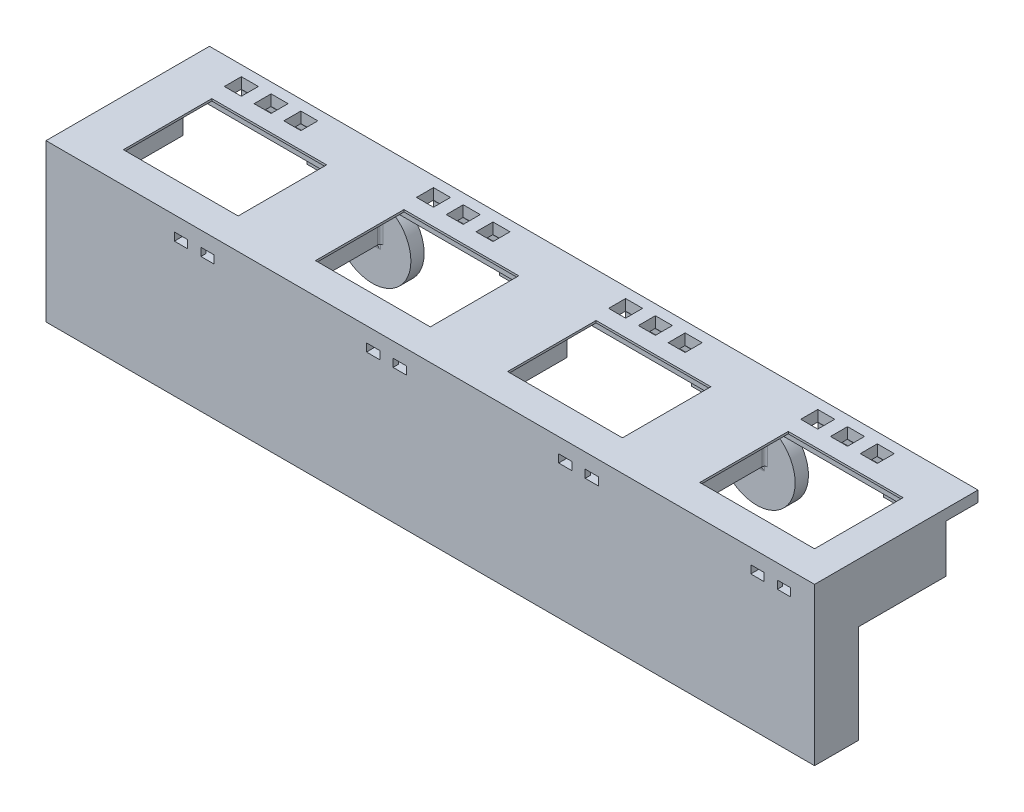
SolidWorks part; units mm, degrees
ref_plane "Front Plane" through (0, 0, 0) normal (0, 0, 1) x (1, 0, 0)
ref_plane "Top Plane" through (0, 0, 0) normal (0, 1, 0) x (1, 0, 0)
ref_plane "Right Plane" through (0, 0, 0) normal (1, 0, 0) x (0, 0, -1)
sketch "Sketch1" plane through (0, 0, 0) normal (0, 1, 0) x (1, 0, 0)
  line L0 (23.7457, 59.297) -> (23.7457, 2.797)
  line L1 (33.7457, 49.297) -> (86.0457, 49.297)
  line L2 (33.7457, 49.297) -> (33.7457, 12.797)
  line L3 (33.7457, 12.797) -> (86.0457, 12.797)
  line L4 (86.0457, 49.297) -> (86.0457, 12.797)
  line L5 (23.7457, 2.797) -> (96.0457, 2.797)
  line L6 (96.0457, 59.297) -> (96.0457, 2.797)
  line L7 (23.7457, 59.297) -> (96.0457, 59.297)
  dimension "D1" = 36.5
  dimension "D2" = 52.3
  dimension "D3" = 10
extrude "Boss-Extrude1" add sketch "Sketch1" along normal blind 3.3
sketch "Sketch2" plane through (0, 0, 0) normal (0, -1, 0) x (1, 0, 0)
  line L0 (96.0457, -2.797) -> (96.0457, -59.297) construction
  line L1 (23.7457, -2.797) -> (96.0457, -2.797)
  line L2 (23.7457, -2.797) -> (23.7457, -4.797)
  line L3 (23.7457, -4.797) -> (96.0457, -4.797)
  line L4 (96.0457, -2.797) -> (96.0457, -4.797)
  dimension "D1" = 2
extrude "Boss-Extrude2" add sketch "Sketch2" along normal blind 45
sketch "Sketch3" plane through (0, 0, -4.797) normal (0, 0, -1) x (-1, 0, 0)
  line L0 (-23.7457, -45) -> (-96.0457, -45) construction
  line L1 (-96.0457, 0) -> (-94.0457, 0)
  line L2 (-96.0457, 0) -> (-96.0457, -45)
  line L3 (-96.0457, -45) -> (-94.0457, -45)
  line L4 (-94.0457, 0) -> (-94.0457, -45)
  line L6 (-23.7457, 0) -> (-25.7457, 0)
  line L7 (-23.7457, 0) -> (-23.7457, -45)
  line L8 (-23.7457, -45) -> (-25.7457, -45)
  line L9 (-25.7457, 0) -> (-25.7457, -45)
  dimension "D1" = 2
  dimension "D2" = 2
extrude "Boss-Extrude3" add sketch "Sketch3" along normal up to surface (54.5 mm away) up to face at (59.8957, 1.65, -59.297)
sketch "Sketch5" plane through (0, 3.3, 0) normal (0, 1, 0) x (1, 0, 0)
  line L1 (23.7457, 59.297) -> (96.0457, 59.297)
  line L2 (23.7457, 59.297) -> (23.7457, 2.797)
  line L3 (23.7457, 2.797) -> (96.0457, 2.797)
  line L4 (96.0457, 59.297) -> (96.0457, 2.797)
  line L9 (41.2457, 47.697) -> (41.2457, 14.397)
  line L10 (41.2457, 47.697) -> (84.4457, 47.697)
  line L11 (84.4457, 47.697) -> (84.4457, 14.397)
  line L12 (84.4457, 14.397) -> (41.2457, 14.397)
  point P6 (34.2457, 48.797)
  point P7 (34.2457, 13.297)
  point P8 (85.5457, 13.297)
  point P9 (85.5457, 48.797)
  dimension "D2" = 11.6
  dimension "D1" = 17.5
  dimension "D3" = 11.6
  dimension "D4" = 11.6
extrude "Boss-Extrude6" add sketch "Sketch5" along normal blind 0.8
sketch "Sketch6" plane through (0, 0, -4.797) normal (0, 0, -1) x (-1, 0, 0)
  line L0 (-25.7457, 0) -> (-25.7457, -45) construction
  line L1 (-94.0457, 0) -> (-25.7457, 0)
  line L2 (-94.0457, 0) -> (-94.0457, -1.5)
  line L3 (-94.0457, -1.5) -> (-25.7457, -1.5)
  line L4 (-25.7457, 0) -> (-25.7457, -1.5)
  dimension "D1" = 1.5
extrude "Boss-Extrude7" add sketch "Sketch6" along normal blind 7.8
sketch "Sketch7" plane through (0, 0, -4.797) normal (0, 0, -1) x (-1, 0, 0)
  line L0 (-94.0457, -1.5) -> (-87.0457, -1.5) construction
  line L1 (-94.0457, -1.5) -> (-25.7457, -1.5) construction
  line L2 (-87.0457, -1.5) -> (-72.0457, -1.5) construction
  line L3 (-87.0457, -1.5) -> (-87.0457, -4.5)
  line L4 (-87.0457, -4.5) -> (-72.0457, -4.5)
  line L5 (-72.0457, -4.5) -> (-72.0457, -1.5)
  line L6 (-72.0457, -1.5) -> (-70.5457, -1.5)
  line L7 (-70.5457, -1.5) -> (-70.5457, -6)
  line L8 (-70.5457, -6) -> (-88.5457, -6)
  line L9 (-88.5457, -6) -> (-88.5457, -1.5)
  line L10 (-88.5457, -1.5) -> (-87.0457, -1.5)
  dimension "D1" = 7
  dimension "D2" = 15
  dimension "D3" = 3
  dimension "D4" = 1.5
  dimension "D5" = 1.5
  dimension "D6" = 1.5
extrude "Boss-Extrude8" add sketch "Sketch7" along normal up to surface (7.8 mm away) up to face at (59.8957, -0.75, -12.597)
sketch "Sketch8" plane through (0, 0, -59.297) normal (0, 0, -1) x (-1, 0, 0)
  line L0 (-94.0457, 0) -> (-25.7457, 0) construction
  line L1 (-88.5457, -6) -> (-70.503, -6)
  line L2 (-88.5457, -6) -> (-88.5457, 0)
  line L3 (-88.5457, 0) -> (-70.503, 0)
  line L4 (-70.503, -6) -> (-70.503, 0)
  line L6 (-87.0457, -1.5) -> (-72.0457, -1.5)
  line L7 (-87.0457, -1.5) -> (-87.0457, -4.5)
  line L8 (-87.0457, -4.5) -> (-72.0457, -4.5)
  line L9 (-72.0457, -1.5) -> (-72.0457, -4.5)
extrude "Boss-Extrude9" add sketch "Sketch8" against normal up to surface (10 mm away) up to face at (59.8957, 1.65, -49.297)
sketch "Sketch9" plane through (0, 0, 0) normal (0, -1, 0) x (1, 0, 0)
  line L0 (86.0457, -49.297) -> (86.0457, -44.297) construction
  line L1 (86.0457, -12.797) -> (86.0457, -49.297) construction
  line L2 (86.0457, -44.297) -> (90.0457, -44.297)
  line L3 (90.0457, -44.297) -> (90.0457, -17.797)
  line L4 (90.0457, -17.797) -> (86.0457, -17.797)
  line L5 (86.0457, -17.797) -> (86.0457, -12.797) construction
  line L6 (86.0457, -44.297) -> (86.0457, -17.797)
  dimension "D1" = 5
  dimension "D2" = 5
  dimension "D3" = 4
extrude "Cut-Extrude1" cut sketch "Sketch9" against normal blind 2
sketch "Sketch10" plane through (0, 0, -59.297) normal (0, 0, -1) x (-1, 0, 0)
  line L0 (-94.0457, 0) -> (-94.0457, -45) construction
  line L1 (-96.0457, -45) -> (-94.0457, -45)
  line L2 (-96.0457, -45) -> (-96.0457, -15)
  line L3 (-96.0457, -15) -> (-94.0457, -15)
  line L4 (-94.0457, -45) -> (-94.0457, -15)
  dimension "D1" = 30
extrude "Cut-Extrude2" cut sketch "Sketch10" against normal blind 40
sketch "Sketch11" plane through (0, -1.5, 0) normal (0, -1, 0) x (1, 0, 0)
  line L0 (94.0457, -4.797) -> (94.0457, -7.197) construction
  line L1 (94.0457, -4.797) -> (88.5457, -4.797) construction
  line L2 (94.0457, -12.597) -> (94.0457, -4.797) construction
  line L3 (94.0457, -7.197) -> (94.0457, -8.197)
  line L4 (94.0457, -8.197) -> (92.0457, -8.197)
  line L5 (92.0457, -8.197) -> (92.0457, -7.197)
  line L6 (92.0457, -7.197) -> (94.0457, -7.197)
  line L7 (25.7457, -7.197) -> (27.7457, -7.197)
  line L8 (25.7457, -12.597) -> (25.7457, -4.797) construction
  line L9 (27.7457, -7.197) -> (27.7457, -8.197)
  line L10 (27.7457, -8.197) -> (25.7457, -8.197)
  line L11 (25.7457, -8.197) -> (25.7457, -7.197)
  line L12 (70.5457, -4.797) -> (25.7457, -4.797) construction
  dimension "D1" = 2.4
  dimension "D2" = 2
  dimension "D3" = 1
  dimension "D4" = 2.4
  dimension "D5" = 1
  dimension "D6" = 2
extrude "Boss-Extrude10" add sketch "Sketch11" along normal blind 20
sketch "Sketch13" plane through (0, 0, -59.297) normal (0, 0, -1) x (-1, 0, 0)
  line L13 (-87.0457, -1.5) -> (-72.0457, -1.5)
  line L14 (-87.0457, -1.5) -> (-87.0457, -4.5)
  line L15 (-87.0457, -4.5) -> (-72.0457, -4.5)
  line L16 (-72.0457, -1.5) -> (-72.0457, -4.5)
  line L24 (-96.0457, 4.1) -> (-96.0457, -15)
  line L25 (-96.0457, -15) -> (-94.0457, -15)
  line L26 (-94.0457, -15) -> (-94.0457, 0)
  line L27 (-94.0457, 0) -> (-88.5457, 0)
  line L28 (-88.5457, 0) -> (-88.5457, -6)
  line L29 (-88.5457, -6) -> (-70.503, -6)
  line L30 (-70.503, -6) -> (-70.503, 0)
  line L31 (-70.503, 0) -> (-25.7457, 0)
  line L32 (-25.7457, 0) -> (-25.7457, -45)
  line L33 (-25.7457, -45) -> (-23.7457, -45)
  line L34 (-23.7457, -45) -> (-23.7457, 4.1)
  line L35 (-23.7457, 4.1) -> (-96.0457, 4.1)
  line L36 (-96.0457, 4.1) -> (-96.0457, -15)
  line L37 (-96.0457, -15) -> (-94.0457, -15)
  line L38 (-94.0457, -15) -> (-94.0457, 0)
  line L39 (-94.0457, 0) -> (-88.5457, 0)
  line L40 (-88.5457, 0) -> (-88.5457, -6)
  line L41 (-88.5457, -6) -> (-70.503, -6)
  line L42 (-70.503, -6) -> (-70.503, 0)
  line L43 (-70.503, 0) -> (-25.7457, 0)
  line L44 (-25.7457, 0) -> (-25.7457, -45)
  line L45 (-25.7457, -45) -> (-23.7457, -45)
  line L46 (-23.7457, -45) -> (-23.7457, 4.1)
  line L47 (-23.7457, 4.1) -> (-96.0457, 4.1)
  dimension "D1" = 0
extrude "Boss-Extrude11" add sketch "Sketch13" along normal blind 5
sketch "Sketch12" plane through (0, 4.1, 0) normal (0, 1, 0) x (1, 0, 0)
  line L0 (23.7457, 60.297) -> (39.7457, 60.297) construction
  line L1 (23.7457, 64.297) -> (23.7457, 2.797) construction
  line L2 (39.7457, 60.297) -> (39.7457, 64.297) construction
  line L4 (45.9457, 60.297) -> (50.9457, 60.297) construction
  line L5 (39.7457, 60.297) -> (45.9457, 60.297)
  line L6 (39.7457, 60.297) -> (39.7457, 54.097)
  line L7 (39.7457, 54.097) -> (45.9457, 54.097)
  line L8 (45.9457, 60.297) -> (45.9457, 54.097)
  line L10 (50.9457, 60.297) -> (57.1457, 60.297)
  line L11 (50.9457, 60.297) -> (50.9457, 54.097)
  line L12 (50.9457, 54.097) -> (57.1457, 54.097)
  line L13 (57.1457, 60.297) -> (57.1457, 54.097)
  line L14 (23.7457, 64.297) -> (96.0457, 64.297) construction
  dimension "D1" = 4
  dimension "D2" = 16
  dimension "D3" = 6.2
  dimension "D4" = 6.2
  dimension "D5" = 5
  dimension "D6" = 6.2
  dimension "D7" = 6.2
extrude "Cut-Extrude3" cut sketch "Sketch12" against normal blind 10
sketch "Sketch14" plane through (0, 0, 0) normal (0, -1, 0) x (1, 0, 0)
  line L0 (88.5457, -49.297) -> (88.5457, -64.297) construction
  line L1 (70.503, -49.297) -> (88.5457, -49.297)
  line L2 (70.503, -49.297) -> (70.503, -54.297)
  line L3 (70.503, -54.297) -> (88.5457, -54.297)
  line L4 (88.5457, -49.297) -> (88.5457, -54.297)
  dimension "D1" = 5
extrude "Cut-Extrude4" cut sketch "Sketch14" along normal blind 25
sketch "Sketch15" plane through (0, 0, -64.297) normal (0, 0, -1) x (-1, 0, 0)
  line L1 (-100.1161, -15.1013) -> (-70.503, -15.1013)
  line L2 (-100.1161, -15.1013) -> (-100.1161, 0)
  line L3 (-100.1161, 0) -> (-70.503, 0)
  line L4 (-70.503, -15.1013) -> (-70.503, 0)
extrude "Cut-Extrude5" cut sketch "Sketch15" against normal blind 2
sketch "Sketch17" plane through (0, 0, 0) normal (0, -1, 0) x (1, 0, 0)
  line L1 (88.5457, -54.297) -> (94.0457, -54.297)
  line L2 (88.5457, -54.297) -> (88.5457, -62.297)
  line L3 (88.5457, -62.297) -> (94.0457, -62.297)
  line L4 (94.0457, -54.297) -> (94.0457, -62.297)
extrude "Boss-Extrude12" add sketch "Sketch17" along normal up to surface (6 mm away) up to face at (79.5244, -6, -58.297)
sketch "Sketch20" plane through (0, 0, -19.297) normal (0, 0, -1) x (-1, 0, 0)
  line L0 (-94.0457, -21.5) -> (-94.0457, -1.5) construction
  line L1 (-96.0457, -15) -> (-94.0457, -15)
  line L2 (-96.0457, -15) -> (-96.0457, -18)
  line L3 (-96.0457, -18) -> (-94.0457, -18)
  line L4 (-94.0457, -15) -> (-94.0457, -18)
  dimension "D1" = 3
extrude "Boss-Extrude14" add sketch "Sketch20" along normal up to surface (43 mm away) up to face at (86.8648, -7, -62.297)
sketch "Sketch21" plane through (0, 0, -62.297) normal (0, 0, -1) x (-1, 0, 0)
  line L0 (-96.0457, -18) -> (-94.0457, -18) construction
  circle A0 centre (-95.0457, -18) radius 14.5
  dimension "D1" = 29
extrude "Boss-Extrude15" add sketch "Sketch21" against normal blind 8
sketch "Sketch22" plane through (0, 0, -62.297) normal (0, 0, -1) x (-1, 0, 0)
  circle A0 centre (-95.0457, -18) radius 12.75
  dimension "D1" = 25.5
extrude "Cut-Extrude6" cut sketch "Sketch22" against normal blind 6
fillet "Fillet1" radius 2 3 edges at (96.0457, -10.7673, -54.297) (95.0457, -18, -54.297) (94.0457, -9, -54.297)
sketch "Sketch23" plane through (0, 0, 0) normal (0, -1, 0) x (1, 0, 0)
  line L1 (39.7457, -54.097) -> (57.154, -54.097)
  line L2 (39.7457, -54.097) -> (39.7457, -53.097)
  line L3 (39.7457, -53.097) -> (57.154, -53.097)
  line L4 (57.154, -54.097) -> (57.154, -53.097)
  dimension "D1" = 1
extrude "Boss-Extrude16" add sketch "Sketch23" along normal blind 2
sketch "Sketch24" plane through (0, 0, -54.097) normal (0, 0, -1) x (-1, 0, 0)
  line L0 (-57.154, -2) -> (-54.754, -2) construction
  line L1 (-39.7457, -2) -> (-57.154, -2) construction
  line L2 (-54.754, -2) -> (-53.3457, -2)
  line L3 (-53.3457, -2) -> (-50.9457, -2) construction
  line L4 (-48.4457, 0) -> (-48.4457, -7.5732) construction
  line L5 (-45.9457, 0) -> (-50.9457, 0) construction
  line L6 (-50.9457, 0) -> (-50.9457, -2) construction
  line L7 (-53.3457, -2) -> (-53.3457, 0)
  line L8 (-53.3457, 0) -> (-54.754, 0)
  line L9 (-54.754, 0) -> (-54.754, -2)
  line L10 (-43.5457, 0) -> (-42.1374, 0)
  line L11 (-43.5457, -2) -> (-43.5457, 0)
  line L12 (-42.1374, -2) -> (-43.5457, -2)
  line L13 (-42.1374, 0) -> (-42.1374, -2)
  dimension "D1" = 2.4
  dimension "D3" = 2.4
extrude "Boss-Extrude17" add sketch "Sketch24" along normal up to surface (8.2 mm away) up to face at (82.2957, -18, -62.297)
sketch "Sketch25" plane through (0, 0, 0) normal (0, -1, 0) x (1, 0, 0)
  line L0 (39.7457, -60.297) -> (57.1457, -60.297)
  line L5 (42.9587, -60.297) -> (42.9587, -62.297) construction
  line L6 (54.754, -62.297) -> (53.3457, -62.297) construction
  line L7 (57.1457, -60.297) -> (57.1457, -62.297)
  line L8 (57.1457, -62.297) -> (39.7457, -62.297)
  line L9 (39.7457, -62.297) -> (39.7457, -60.297)
extrude "Boss-Extrude18" add sketch "Sketch25" along normal blind 2
sketch "Sketch26" plane through (0, 4.1, 0) normal (0, 1, 0) x (1, 0, 0)
  line L23 (39.6457, 53.997) -> (46.0457, 53.997)
  line L24 (39.6457, 60.397) -> (39.6457, 53.997)
  line L25 (46.0457, 60.397) -> (39.6457, 60.397)
  line L26 (46.0457, 53.997) -> (46.0457, 60.397)
  line L27 (39.6457, 53.997) -> (46.0457, 53.997)
  line L28 (39.6457, 60.397) -> (39.6457, 53.997)
  line L29 (46.0457, 60.397) -> (39.6457, 60.397)
  line L30 (46.0457, 53.997) -> (46.0457, 60.397)
  line L41 (50.8457, 53.997) -> (57.2457, 53.997)
  line L42 (57.2457, 53.997) -> (57.2457, 60.397)
  line L43 (57.2457, 60.397) -> (50.8457, 60.397)
  line L44 (50.8457, 60.397) -> (50.8457, 53.997)
  line L45 (50.8457, 53.997) -> (57.2457, 53.997)
  line L46 (57.2457, 53.997) -> (57.2457, 60.397)
  line L47 (57.2457, 60.397) -> (50.8457, 60.397)
  line L48 (50.8457, 60.397) -> (50.8457, 53.997)
  dimension "D1" = 0.1
  dimension "D2" = 0.1
extrude "Cut-Extrude7" cut sketch "Sketch26" against normal up to surface (4.1 mm away) up to face at (48.4457, 0, -57.197)
sketch "Sketch28" plane through (0, 0, -4.797) normal (0, 0, -1) x (-1, 0, 0)
  line L0 (-87.0457, -4.5) -> (-72.0457, -4.5) construction
  line L1 (-87.0457, -1.5) -> (-82.0457, -1.5)
  line L2 (-87.0457, -1.5) -> (-87.0457, -4.5)
  line L3 (-87.0457, -4.5) -> (-82.0457, -4.5)
  line L4 (-82.0457, -1.5) -> (-82.0457, -4.5)
  line L5 (-82.0457, -1.5) -> (-77.0457, -1.5) construction
  line L6 (-72.0457, -1.5) -> (-77.0457, -1.5)
  line L7 (-72.0457, -1.5) -> (-72.0457, -4.5)
  line L8 (-72.0457, -4.5) -> (-77.0457, -4.5)
  line L9 (-77.0457, -1.5) -> (-77.0457, -4.5)
  dimension "D1" = 5
  dimension "D2" = 5
extrude "Cut-Extrude9" cut sketch "Sketch28" against normal up to surface (2 mm away) up to face at (59.8957, -20.45, -2.797)
sketch "Sketch29" plane through (0, 0, -62.297) normal (0, 0, -1) x (-1, 0, 0)
  circle A0 centre (-95.0457, -18) radius 14.5
  circle A1 centre (-95.0457, -18) radius 12.75
extrude "Cut-Extrude10" cut sketch "Sketch29" against normal blind 3
fillet "Fillet2" radius 10 1 edges at (96.0457, -3.5345, -55.797)
sketch "Sketch30" plane through (0, -45, 0) normal (0, -1, 0) x (1, 0, 0)
  line L16 (94.0457, -19.297) -> (96.0457, -19.297)
  line L17 (96.0457, -19.297) -> (96.0457, -2.797)
  line L18 (96.0457, -2.797) -> (23.7457, -2.797)
  line L19 (23.7457, -2.797) -> (23.7457, -64.297)
  line L20 (23.7457, -64.297) -> (25.7457, -64.297)
  line L21 (25.7457, -64.297) -> (25.7457, -4.797)
  line L22 (25.7457, -4.797) -> (94.0457, -4.797)
  line L23 (94.0457, -4.797) -> (94.0457, -19.297)
  line L24 (94.0457, -19.297) -> (96.0457, -19.297)
  line L25 (96.0457, -19.297) -> (96.0457, -2.797)
  line L26 (96.0457, -2.797) -> (23.7457, -2.797)
  line L27 (23.7457, -2.797) -> (23.7457, -64.297)
  line L28 (23.7457, -64.297) -> (25.7457, -64.297)
  line L29 (25.7457, -64.297) -> (25.7457, -4.797)
  line L30 (25.7457, -4.797) -> (94.0457, -4.797)
  line L31 (94.0457, -4.797) -> (94.0457, -19.297)
  dimension "D1" = 0
extrude "Boss-Extrude19" add sketch "Sketch30" along normal blind 10
sketch "Sketch31" plane through (25.7457, 0, 0) normal (1, 0, 0) x (0, 0, -1)
  line L0 (19.297, -55) -> (19.297, -18)
  line L1 (19.297, -18) -> (52.297, -18)
  line L2 (52.297, -18) -> (52.297, 0)
  line L3 (64.297, 0) -> (12.597, 0) construction
  line L4 (52.297, 0) -> (64.297, 0)
  line L5 (64.297, 0) -> (64.297, -55)
  line L6 (64.297, -55) -> (19.297, -55)
extrude "Cut-Extrude11" cut sketch "Sketch31" against normal blind 10
pattern_linear "LPattern3" count 4 spacing 72.3 along (1, 0, 0) of bodies 134
sketch "Sketch32" plane through (0, 0, -64.297) normal (0, 0, -1) x (-1, 0, 0)
  line L0 (-303.9457, -3) -> (-305.4857, -3) construction
  line L1 (-303.9457, -1.5) -> (-303.9457, -4.5) construction
  line L2 (-305.4857, 0) -> (-305.4857, -6.0069)
  line L3 (-287.403, 0) -> (-312.9457, 0) construction
  line L4 (-305.4857, -6.0069) -> (-303.8063, -6)
  line L5 (-303.8063, -6) -> (-292.5605, -10.935)
  line L6 (-292.5605, -10.935) -> (-292.5605, -41.4968)
  line L7 (-292.5605, -41.4968) -> (-337.3057, -41.4968)
  line L8 (-337.3057, -41.4968) -> (-337.3057, 6.0345)
  line L9 (-337.3057, 6.0345) -> (-312.9457, 6.0345)
  line L10 (-312.9457, 6.0345) -> (-312.9457, 0)
  line L11 (-312.9457, 0) -> (-305.4857, 0)
  line L13 (-168.1457, 0) -> (-160.6857, 0)
  line L14 (-160.6857, 0) -> (-160.6857, -6.0069)
  line L15 (-160.6857, -6.0069) -> (-159.0063, -6)
  line L16 (-159.0063, -6) -> (-147.7605, -10.935)
  line L17 (-147.7605, -10.935) -> (-147.7605, -41.4968)
  line L18 (-147.7605, -41.4968) -> (-192.5057, -41.4968)
  line L19 (-192.5057, -41.4968) -> (-192.5057, -13.9836)
  line L21 (-168.1457, 0) -> (-173.9513, 0)
  line L22 (-240.6457, 0) -> (-168.3457, 0) construction
  line L23 (-173.9513, 0) -> (-192.5057, -13.9836)
  line L25 (-192.5057, 6.0345) -> (-168.1457, 6.0345) [skipped]
  line L26 (-168.1457, 6.0345) -> (-168.1457, 0) [skipped]
  dimension "D1" = 1.54
  dimension "D2" = 2
extrude "Cut-Extrude12" cut sketch "Sketch32" against normal up to vertex (12 mm away) up to point (240.6457, 0, -52.297)
sketch "Sketch33" plane through (0, 0, -62.297) normal (0, 0, -1) x (-1, 0, 0)
  line L1 (-305.4857, 0) -> (-287.4457, 0)
  line L2 (-305.4857, 0) -> (-305.4857, -6)
  line L3 (-305.4857, -6) -> (-287.4457, -6)
  line L4 (-287.4457, 0) -> (-287.4457, -6)
  line L5 (-303.9457, -1.5) -> (-288.9457, -1.5)
  line L6 (-303.9457, -1.5) -> (-303.9457, -4.5)
  line L7 (-303.9457, -4.5) -> (-288.9457, -4.5)
  line L8 (-288.9457, -1.5) -> (-288.9457, -4.5)
  line L9 (-160.6857, 0) -> (-142.8457, 0)
  line L10 (-160.6857, 0) -> (-160.6857, -6)
  line L11 (-160.6857, -6) -> (-142.8457, -6)
  line L12 (-142.8457, 0) -> (-142.8457, -6)
  line L13 (-159.3457, -1.5) -> (-144.3457, -1.5)
  line L14 (-159.3457, -1.5) -> (-159.3457, -4.5)
  line L15 (-159.3457, -4.5) -> (-144.3457, -4.5)
  line L16 (-144.3457, -1.5) -> (-144.3457, -4.5)
extrude "Boss-Extrude20" add sketch "Sketch33" against normal up to surface (8 mm away) up to face at (154.2315, -4.0013, -54.297)
sketch "Sketch34" plane through (0, 0, 0) normal (0, -1, 0) x (1, 0, 0)
  line L0 (254.1457, -54.297) -> (225.1457, -54.297) construction
  line L1 (242.6457, -52.297) -> (240.6457, -52.297)
  line L2 (242.6457, -52.297) -> (242.6457, -54.297)
  line L3 (242.6457, -54.297) -> (240.6457, -54.297)
  line L4 (240.6457, -52.297) -> (240.6457, -54.297)
  line L5 (96.0457, -64.297) -> (96.0457, -52.297) construction
  line L6 (98.0457, -52.297) -> (96.0457, -52.297)
  line L7 (98.0457, -52.297) -> (98.0457, -54.297)
  line L8 (98.0457, -54.297) -> (96.0457, -54.297)
  line L9 (96.0457, -52.297) -> (96.0457, -54.297)
extrude "Boss-Extrude21" add sketch "Sketch34" along normal up to surface (18 mm away) up to face at (169.3457, -18, -35.797)
fillet "Fillet3" radius 1 2 edges at (98.0457, -10.0541, -54.297) (242.6457, -10.0541, -54.297)
sketch "Sketch35" plane through (0, 0, -4.797) normal (0, 0, -1) x (-1, 0, 0)
  line L0 (-166.3457, -55) -> (-166.3457, -1.5) construction
  line L1 (-164.3457, -1.5) -> (-166.3457, -1.5)
  line L2 (-164.3457, -1.5) -> (-164.3457, -21.5)
  line L3 (-164.3457, -21.5) -> (-166.3457, -21.5)
  line L4 (-166.3457, -1.5) -> (-166.3457, -21.5)
  line L5 (-164.3457, -21.5) -> (-166.3457, -21.5) construction
extrude "Cut-Extrude14" cut sketch "Sketch35" along normal up to surface (3.4 mm away) up to face at (165.3457, -11.5, -8.197)
sketch "Sketch36" plane through (0, 0, -4.797) normal (0, 0, -1) x (-1, 0, 0)
  line L0 (-166.3457, -1.5) -> (-160.8457, -1.5)
  line L1 (-160.8457, -1.5) -> (-160.8457, -6)
  line L2 (-160.8457, -6) -> (-142.8457, -6)
  line L3 (-142.8457, -6) -> (-142.8457, -55)
  line L4 (-98.0457, -55) -> (-166.3457, -55) construction
  line L5 (-142.8457, -55) -> (-166.3457, -55)
  line L6 (-166.3457, -55) -> (-166.3457, -1.5)
extrude "Boss-Extrude22" add sketch "Sketch36" along normal up to surface (3.4 mm away) up to face at (99.0457, -11.5, -8.197)
sketch "Sketch37" plane through (0, 0, -8.197) normal (0, 0, -1) x (-1, 0, 0)
  line L0 (-100.0457, -21.5) -> (-142.8457, -21.5) construction
  line L1 (-142.8457, -6) -> (-142.8457, -55) construction
  line L2 (-121.4457, -21.5) -> (-121.4457, -31.7135) construction
  line L8 (-142.8457, -21.5) -> (-140.8457, -21.5)
  line L9 (-142.8457, -21.5) -> (-142.8457, -1.5)
  line L10 (-142.8457, -1.5) -> (-140.8457, -1.5)
  line L11 (-140.8457, -21.5) -> (-140.8457, -1.5)
  dimension "D1" = 2
extrude "Boss-Extrude23" add sketch "Sketch37" against normal up to vertex (1 mm away) up to point (100.0457, -21.5, -7.197)
sketch "Sketch38" plane through (0, 0, -8.197) normal (0, 0, -1) x (-1, 0, 0)
  line L1 (-166.3457, -55) -> (-154.6457, -55)
  line L2 (-166.3457, -55) -> (-166.3457, -11)
  line L3 (-166.3457, -11) -> (-154.6457, -11)
  line L4 (-154.6457, -55) -> (-154.6457, -11)
  dimension "D1" = 11.7
  dimension "D2" = 44
extrude "Cut-Extrude15" cut sketch "Sketch38" against normal up to surface (3.4 mm away) up to face at (120.4457, -28.25, -4.797)
sketch "Sketch39" plane through (0, 0, -4.797) normal (0, 0, -1) x (-1, 0, 0)
  line L0 (-166.3457, -11) -> (-166.3457, -55) construction
  line L1 (-154.6457, -55) -> (-166.3457, -55)
  line L2 (-154.6457, -55) -> (-154.6457, -47)
  line L3 (-154.6457, -47) -> (-166.3457, -47)
  line L4 (-166.3457, -55) -> (-166.3457, -47)
  dimension "D1" = 8
extrude "Boss-Extrude24" add sketch "Sketch39" along normal blind 9.6
ref_plane "Plane1" through (54.0457, 0, 0) normal (1, 0, 0) x (0, 0, -1)
mirror "Mirror1" about plane through (54.0457, 0, 0) normal (1, 0, 0) of "Boss-Extrude18", "Cut-Extrude7", "Boss-Extrude16", "Boss-Extrude17"
pattern_linear "LPattern4" count 4 spacing 72.3 along (1, 0, 0) of "Mirror1"
